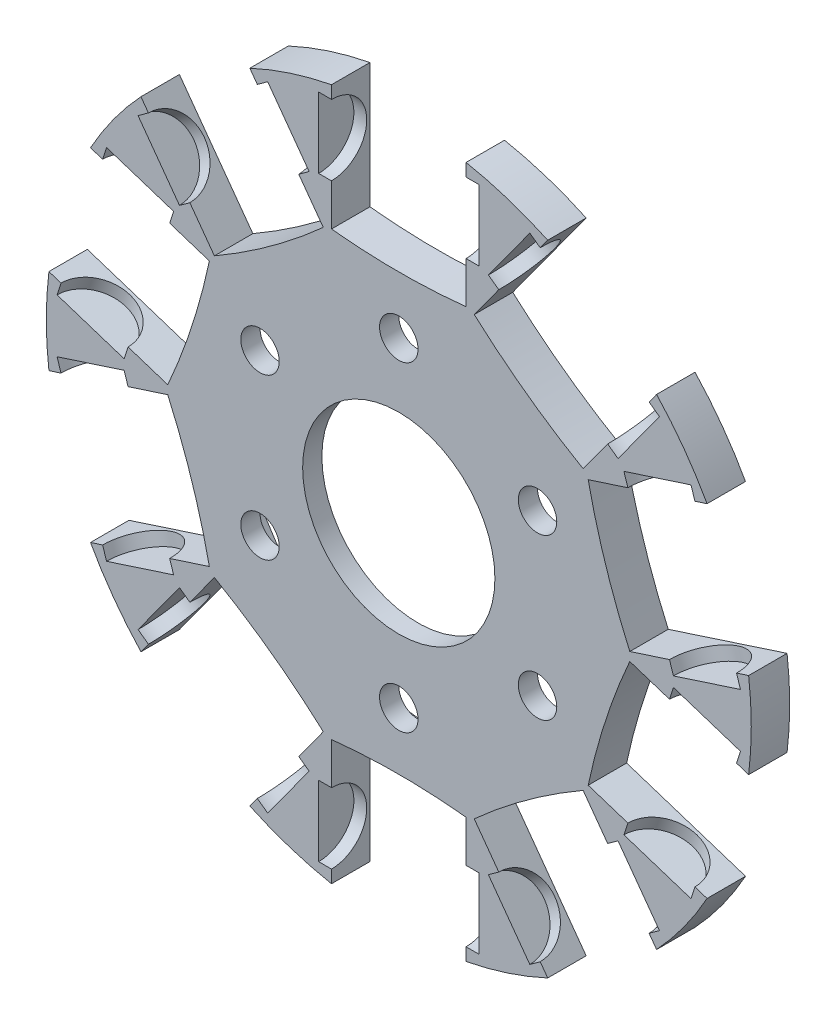
SolidWorks part; units mm, degrees
ref_plane "Front Plane" through (0, 0, 0) normal (0, 0, 1) x (1, 0, 0)
ref_plane "Top Plane" through (0, 0, 0) normal (0, 1, 0) x (1, 0, 0)
ref_plane "Right Plane" through (0, 0, 0) normal (1, 0, 0) x (0, 0, -1)
sketch "Sketch2" plane through (0, 0, 0) normal (0, 0, 1) x (1, 0, 0)
  line L0 (0, -2.3056) -> (0, 37.2834) construction
  line L1 (-5.25, 28.5556) -> (5.25, 28.5556) construction
  line L2 (-5.25, 26.9942) -> (-5.25, 17.2442)
  line L3 (5.25, 26.9942) -> (5.25, 17.2442)
  line L4 (11.6195, 24.9246) -> (5.8886, 17.0367)
  line L5 (20.1141, 18.7529) -> (14.3832, 10.865)
  line L6 (24.0507, 13.3347) -> (14.7779, 10.3218)
  line L7 (27.2954, 3.3486) -> (18.0226, 0.3357)
  line L8 (27.2954, -3.3486) -> (18.0226, -0.3357)
  line L9 (24.0507, -13.3347) -> (14.7779, -10.3218)
  line L10 (20.1141, -18.7529) -> (14.3832, -10.865)
  line L11 (11.6195, -24.9246) -> (5.8886, -17.0367)
  line L12 (5.25, -26.9942) -> (5.25, -17.2442)
  line L13 (-5.25, -26.9942) -> (-5.25, -17.2442)
  line L14 (-11.6195, -24.9246) -> (-5.8886, -17.0367)
  line L15 (-20.1141, -18.7529) -> (-14.3832, -10.865)
  line L16 (-24.0507, -13.3347) -> (-14.7779, -10.3218)
  line L17 (-27.2954, -3.3486) -> (-18.0226, -0.3357)
  line L18 (-27.2954, 3.3486) -> (-18.0226, 0.3357)
  line L19 (-24.0507, 13.3347) -> (-14.7779, 10.3218)
  line L20 (-20.1141, 18.7529) -> (-14.3832, 10.865)
  line L21 (-11.6195, 24.9246) -> (-5.8886, 17.0367)
  circle A0 centre (0, 0) radius 27.5
  circle A1 centre (0, 0) radius 12.5 construction
  circle A2 centre (0, 0) radius 15.5 construction
  circle A3 centre (-10.8253, 6.25) radius 1.5
  circle A4 centre (0, 12.5) radius 1.5
  circle A5 centre (10.8253, 6.25) radius 1.5
  circle A6 centre (10.8253, -6.25) radius 1.5
  circle A7 centre (0, -12.5) radius 1.5
  circle A8 centre (-10.8253, -6.25) radius 1.5
  arc A9 (-5.25, 17.2442) -> (5.25, 17.2442) centre (0, 66.9678) ccw
  arc A10 (5.8886, 17.0367) -> (14.3832, 10.865) centre (39.3627, 54.1781) ccw
  arc A11 (14.7779, 10.3218) -> (18.0226, 0.3357) centre (63.6902, 20.6942) ccw
  arc A12 (18.0226, -0.3357) -> (14.7779, -10.3218) centre (63.6902, -20.6942) ccw
  arc A13 (14.3832, -10.865) -> (5.8886, -17.0367) centre (39.3627, -54.1781) ccw
  arc A14 (5.25, -17.2442) -> (-5.25, -17.2442) centre (0, -66.9678) ccw
  arc A15 (-5.8886, -17.0367) -> (-14.3832, -10.865) centre (-39.3627, -54.1781) ccw
  arc A16 (-14.7779, -10.3218) -> (-18.0226, -0.3357) centre (-63.6902, -20.6942) ccw
  arc A17 (-18.0226, 0.3357) -> (-14.7779, 10.3218) centre (-63.6902, 20.6942) ccw
  arc A18 (-14.3832, 10.865) -> (-5.8886, 17.0367) centre (-39.3627, 54.1781) ccw
  circle A19 centre (0, 0) radius 7.5
  circle A20 centre (0, 0) radius 15.5
  point P9 (0, 28.5556)
  point P25 (0, 0)
  point P75 (0, 0)
  point P79 (0, 0)
  point P80 (0, 0)
  point P81 (0, 0)
  point P83 (-22.6761, 7.3679)
  dimension "D1" = 55
  dimension "D2" = 10.5
  dimension "37" = 25
  dimension "D3" = 10
  dimension "35" = 31
  dimension "D4" = 3
  dimension "D8" = 15
  dimension "D7" = 50
  dimension "D6" = 9.75
  dimension "D5" = 6
extrude "Boss-Extrude2" add sketch "Sketch2" along normal blind 3 contours A0 L3 A9 L2 A20 | A20 A3 A4 A5 A6 A7 A8 A19 region at (-6.0207, 22.1192, 0) region at (-15.0616, 0, 0)
extrude "Boss-Extrude3" add sketch "Sketch2<4>" along normal blind 3 contours A20 A8 A1 A3 A4 A5 A6 A7 region at (-15.0616, 0, 0)
sketch "Sketch2<4>" plane through (0, 0, 0) normal (0, 0, 1) x (1, 0, 0) same geometry as "Sketch2"
sketch "Sketch3" plane through (0, 0, 3) normal (0, 0, 1) x (1, 0, 0)
  line L0 (0, 28.1882) -> (0, 8.7236) construction
  line L1 (-4.625, 27.1083) -> (4.625, 27.1083) construction
  line L3 (-6.683, 23) -> (6.8867, 23) construction
  line L4 (-6.25, 26) -> (6.25, 26)
  line L5 (6.25, 26) -> (6.25, 23.25)
  line L6 (-6.25, 26) -> (-6.25, 23.25)
  line L7 (6.25, 23.25) -> (-6.25, 23.25)
  point P15 (0, 26)
  dimension "D1" = 23
  dimension "D2" = 12.5
  dimension "D3" = 3
  dimension "D4" = 2.75
revolve "Cut-Revolve1" cut sketch "Sketch3" angle 360 about L7
sketch "Sketch5" plane through (0, 0, 0) normal (0, 0, -1) x (-1, 0, 0)
  circle A0 centre (0, 0) radius 15.5
  dimension "D1" = 31
extrude "Cut-Extrude2" cut sketch "Sketch5" against normal blind 1.5
pattern_circular "CirPattern1" count 10 over 360 about axis through (0, 0, 3) along (0, 0, 1) of "Cut-Revolve1"
